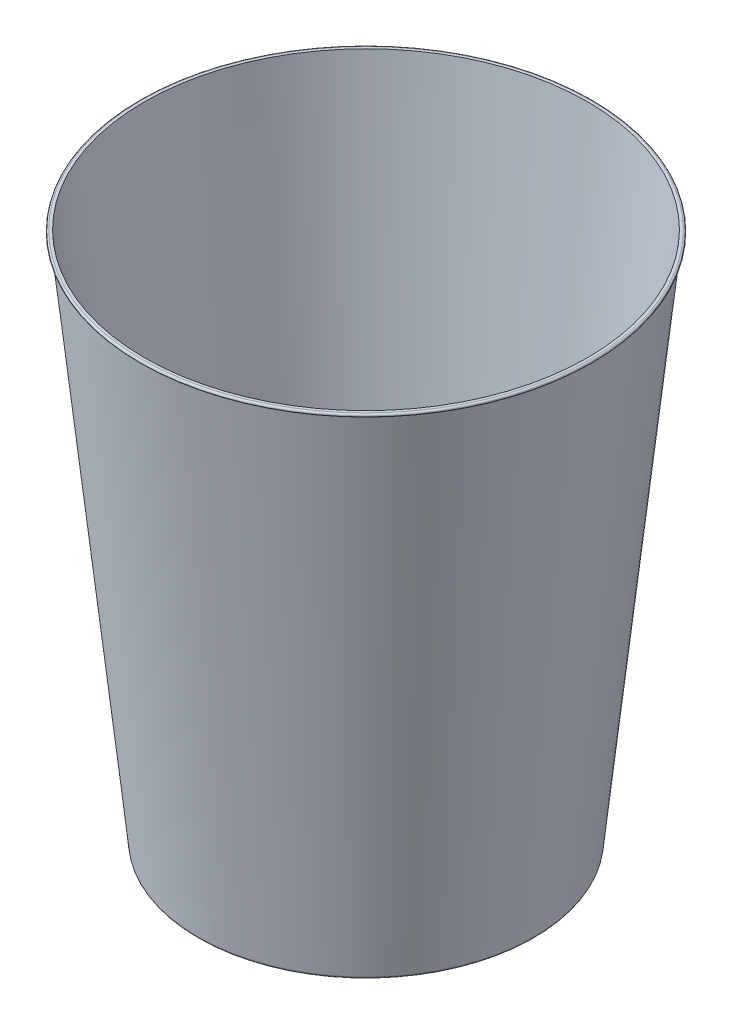
SolidWorks part; units mm, degrees
ref_plane "Front Plane" through (0, 0, 0) normal (0, 0, 1) x (1, 0, 0)
ref_plane "Top Plane" through (0, 0, 0) normal (0, 1, 0) x (1, 0, 0)
ref_plane "Right Plane" through (0, 0, 0) normal (1, 0, 0) x (0, 0, -1)
sketch "Sketch1" plane through (0, 0, 0) normal (0, 1, 0) x (1, 0, 0)
  circle A0 centre (0, 0) radius 35
extrude "Boss-Extrude2" add sketch "Sketch1" against normal blind 83 draft 6 contours A0
shell "Shell2" thickness 0.3 removed face at (0, 0, 35)
fillet "Fillet3" radius 0.3 2 edges at (0, -83, 26.2763) (0, 0, 35)
sketch "Sketch3" plane through (0, 0, 0) normal (1, 0, 0) x (0, 0, -1)
  line L0 (34.6983, 0) -> (35.1183, 0)
  line L1 (35.0503, -0.4194) -> (35.0758, -0.372)
  line L2 (35.0318, -0.2984) -> (34.967, -0.2984)
  line L3 (0, 0) -> (0, 10.9744) construction
  line L4 (-34.6983, 0) -> (34.6983, 0) construction
  line L5 (0, 10.9744) -> (0, -12.5366) construction
  line L6 (34.6983, 0) -> (34.967, -0.2984)
  arc A0 (35.1183, 0) -> (35.0824, -0.4916) centre (35.1421, -0.2489) cw
  arc A1 (34.9653, -0.3297) -> (34.6983, 0) centre (34.667, -0.2984) ccw construction
  arc A2 (35.0824, -0.4916) -> (35.0503, -0.4194) centre (35.0944, -0.4431) cw
  arc A3 (35.0758, -0.372) -> (35.0318, -0.2984) centre (35.0318, -0.3484) ccw
  dimension "D1" = 0.05
revolve "Revolve1" add sketch "Sketch3" angle 360 about L3
